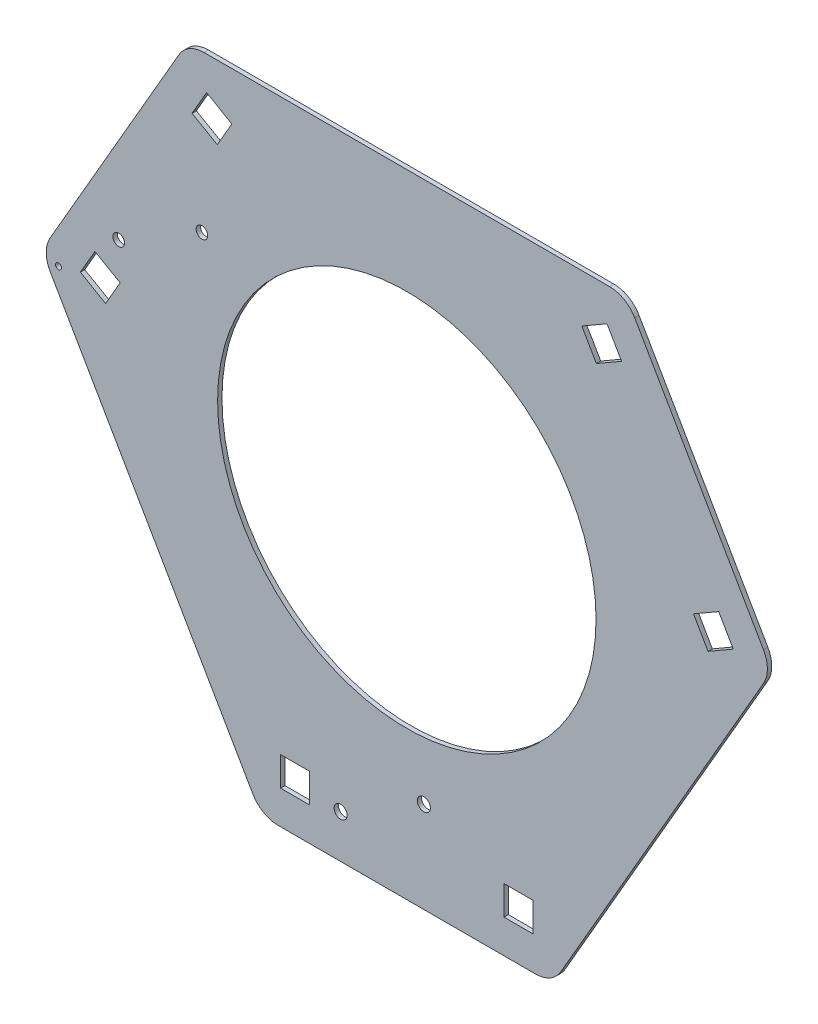
SolidWorks part; units mm, degrees
ref_plane "前视基准面" through (0, 0, 0) normal (0, 0, 1) x (1, 0, 0)
ref_plane "上视基准面" through (0, 0, 0) normal (0, 1, 0) x (1, 0, 0)
ref_plane "右视基准面" through (0, 0, 0) normal (1, 0, 0) x (0, 0, -1)
other "Configuration Table"
sketch "草图1" plane through (0, 0, 0) normal (0, 0, 1) x (1, 0, 0)
  line L0 (150.8286, 202.551) -> (-150.8286, 202.551)
  line L1 (-150.8286, 202.551) -> (-250.8286, 29.3459)
  line L2 (-250.8286, 29.3459) -> (-100, -231.8969)
  line L3 (-100, -231.8969) -> (100, -231.8969)
  line L4 (100, -231.8969) -> (250.8286, 29.3459)
  line L6 (-200.8286, 115.9485) -> (175.4143, -101.2755) construction
  line L7 (0, 202.551) -> (0, -231.8969) construction
  line L8 (-175.4143, -101.2755) -> (200.8262, 115.9471)
  line L9 (150.8286, 202.551) -> (250.8286, 29.3459)
  circle A0 centre (0, 0) radius 130
  circle A27 centre (11.6831, -169.2956) radius 4.5
  circle A47 centre (-140.7727, 94.7657) radius 4
  circle A49 centre (-197.9304, 61.7657) radius 4
  circle A51 centre (-45.4745, -202.2956) radius 4.5
  circle A58 centre (-239.2965, 25.3195) radius 2
  circle A72 centre (55.7209, -177.8966) radius 2
  circle A74 centre (97.7209, -177.8966) radius 2
  circle A76 centre (55.7209, -219.8966) radius 2
  circle A78 centre (97.7209, -219.8966) radius 2
  point P7 (0, 0)
  point P16 (-45.4745, -202.2956)
  point P70 (-122.2962, -44.0868)
  dimension "D7" = 9
  dimension "D3" = 260
  dimension "D1" = 120
  dimension "D2" = 120
  dimension "D4" = 8
  dimension "D5" = 8
  dimension "D6" = 200
  dimension "D9" = 9
extrude "凸台-拉伸1" add sketch "草图1" along normal blind 3 contours A0 L2 L3 L4 L9 L0 L1 A78 A76 A74 A72 A58 | A74 | A78 | A76 | A72 region at (169.6671, -97.9573, 0) region at (97.7209, -177.8966, 0) region at (55.7209, -219.8966, 0) region at (97.7209, -219.8966, 0)
sketch "草图8" plane through (0, 0, 3) normal (0, 0, 1) x (1, 0, 0)
  line L0 (-137.5496, 179.551) -> (-147.5496, 162.2305)
  line L1 (-137.5496, 179.551) -> (-120.229, 169.551)
  line L2 (-147.5496, 162.2305) -> (-130.229, 152.2305)
  line L3 (-120.229, 169.551) -> (-130.229, 152.2305)
  line L4 (-150.8286, 202.551) -> (-250.8286, 29.3459) construction
  line L5 (-214.2705, 46.6664) -> (-224.2705, 29.3459)
  line L6 (-214.2705, 46.6664) -> (-196.95, 36.6664)
  line L7 (-224.2705, 29.3459) -> (-206.95, 19.3459)
  line L8 (-196.95, 36.6664) -> (-206.95, 19.3459)
  line L9 (-86.7209, -208.8969) -> (-66.7209, -208.8969)
  line L10 (-86.7209, -208.8969) -> (-86.7209, -188.8969)
  line L11 (-66.7209, -208.8969) -> (-66.7209, -188.8969)
  line L12 (-86.7209, -188.8969) -> (-66.7209, -188.8969)
  line L13 (66.7209, -208.8969) -> (86.7209, -208.8969)
  line L14 (66.7209, -208.8969) -> (66.7209, -188.8969)
  line L15 (86.7209, -208.8969) -> (86.7209, -188.8969)
  line L16 (66.7209, -188.8969) -> (86.7209, -188.8969)
  line L17 (224.2705, 29.3459) -> (214.2705, 46.6664)
  line L18 (224.2705, 29.3459) -> (206.95, 19.3459)
  line L19 (214.2705, 46.6664) -> (196.95, 36.6664)
  line L20 (206.95, 19.3459) -> (196.95, 36.6664)
  line L21 (137.5496, 179.551) -> (147.5496, 162.2305)
  line L22 (137.5496, 179.551) -> (120.229, 169.551)
  line L23 (147.5496, 162.2305) -> (130.229, 152.2305)
  line L24 (120.229, 169.551) -> (130.229, 152.2305)
  line L25 (-150.8286, 202.551) -> (-250.8286, 29.3459) construction
  line L26 (250.8286, 29.3459) -> (150.8286, 202.551) construction
  line L27 (-100, -231.8969) -> (100, -231.8969) construction
  line L28 (-150.8286, 202.551) -> (-50.8286, 29.3459) construction
  line L29 (-50.8286, 29.3459) -> (-250.8286, 29.3459) construction
  line L30 (150.8286, 202.551) -> (50.8286, 29.3459) construction
  line L31 (50.8286, 29.3459) -> (250.8286, 29.3459) construction
  line L32 (-100, -231.8969) -> (0, -58.6918) construction
  line L33 (0, -58.6918) -> (100, -231.8969) construction
  dimension "D1" = 20
  dimension "D2" = 20
  dimension "D3" = 20
  dimension "D4" = 20
  dimension "D5" = 20
  dimension "D6" = 20
  dimension "D7" = 20
  dimension "D8" = 20
  dimension "D9" = 20
  dimension "D10" = 20
  dimension "D11" = 23
  dimension "D12" = 23
  dimension "D13" = 23
  dimension "D14" = 23
  dimension "D15" = 23
  dimension "D16" = 60
  dimension "D17" = 60
  dimension "D18" = 60
  dimension "D19" = 60
  dimension "D20" = 60
  dimension "D21" = 20
  dimension "D22" = 20
extrude "切除-拉伸4" cut sketch "草图8" against normal through all contours L0 L1 L3 L2 | L5 L6 L8 L7 | L21 L22 L24 L23 | L17 L18 L20 L19 | L9 L10 L12 L11 | L13 L14 L16 L15
fillet "圆角2" radius 20 6 edges at (100, -231.8969, 1.5) (-100, -231.8969, 1.5) (150.8286, 202.551, 1.5) (250.8286, 29.3459, 1.5) (-250.8286, 29.3459, 1.5) (-150.8286, 202.551, 1.5)
